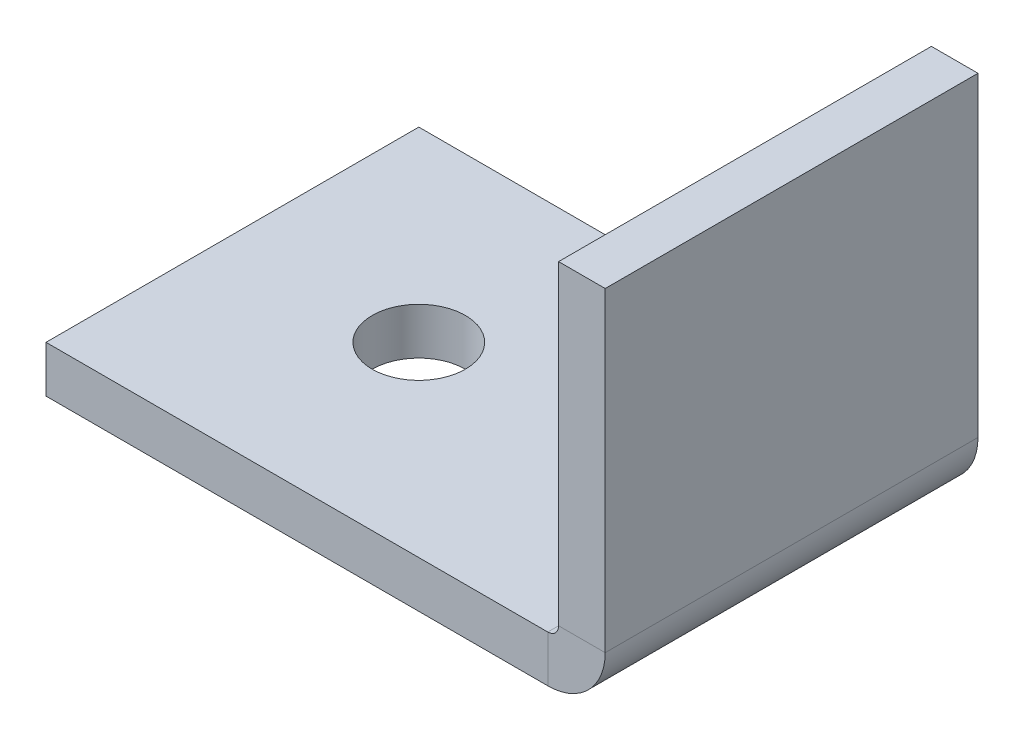
SolidWorks part; units mm, degrees
note: The reader was unsure of these and kept them because the rebuilt part matched: flange length of "Edge-Flange1".
ref_plane "Front Plane" through (0, 0, 0) normal (0, 0, 1) x (1, 0, 0)
ref_plane "Top Plane" through (0, 0, 0) normal (0, 1, 0) x (1, 0, 0)
ref_plane "Right Plane" through (0, 0, 0) normal (1, 0, 0) x (0, 0, -1)
sketch "Sketch1" plane through (0, 0, 0) normal (0, 1, 0) x (1, 0, 0)
  line L1 (-19.05, -12.7) -> (19.05, -12.7)
  line L2 (-19.05, -12.7) -> (-19.05, 12.7)
  line L3 (-19.05, 12.7) -> (19.05, 12.7)
  line L4 (19.05, -12.7) -> (19.05, 12.7)
  line L5 (-19.05, -12.7) -> (19.05, 12.7) construction
  line L6 (-19.05, 12.7) -> (19.05, -12.7) construction
  point P0 (0, 0)
  dimension "D1" = 25.4
  dimension "D2" = 38.1
base flange "Base-Flange1" sketch "Sketch1" thickness 3.175 reverse thickness direction no parameters "D1"=0.7366
edge flange "Edge-Flange1" sketch "Sketch9" flange angle 90 flange length 25.4 flange position material inside bend radius 0.7366 thickness 3.175 relief rectangular parameters "D6"=10
sketch "Sketch9" plane through (19.05, 0, 0) normal (1, 0, 0) x (0, 0, -1)
  line L2 (-12.7, 0) -> (-12.7, 22.225)
  line L3 (-12.7, 22.225) -> (12.7, 22.225)
  line L4 (12.7, 22.225) -> (12.7, 0)
  line L7 (-12.7, 0) -> (12.7, 0) construction
  line L8 (-12.7, 0) -> (12.7, 0)
bend "EdgeBend1" bend radius 0.7366 bend angle 90 parameters "D5"=1
sketch "Sketch10" plane through (0, 0, 0) normal (0, 1, 0) x (1, 0, 0)
  line L1 (19.05, 12.7) -> (19.05, -12.7) construction
  circle A1 centre (-6.35, 0) radius 3.175
  dimension "D1" = 6.35
  dimension "D2" = 25.4
extrude "Cut-Extrude1" cut sketch "Sketch10" against normal through all contours A1 normal cut yes
sketch "Bend-Lines1" [suppressed] plane through (0, 0, 0) normal (0, 1, 0) x (1, 0, 0)
sketch "Bounding-Box1" [suppressed] plane through (0, 0, 0) normal (0, 1, 0) x (1, 0, 0)
sheet metal parameters "Sheet-Metal1" thickness 3.175 parameters "D1"=0.7366
flat pattern "Flat-Pattern1" [suppressed]
sketch "Bend-Lines2" plane through (0, 0, 0) normal (0, 1, 0) x (1, 0, 0)
sketch3d "Bounding-Box2" [suppressed]
  line L0 (19.05, 12.7, 0) -> (-19.05, 12.7, 0) construction
  line L1 (19.05, -12.7, 0) -> (-19.05, -12.7, 0) construction
  line L2 (19.05, 12.7, 0) -> (19.05, -12.7, 0) construction
  line L3 (-19.05, 12.7, 0) -> (-19.05, -12.7, 0) construction
sheet metal parameters "Sheet-Metal2" thickness 3.175 parameters "D1"=0.7366
flat pattern "Flat-Pattern1"
sketch "Bend-Lines2" plane through (0, 0, 0) normal (0, 1, 0) x (1, 0, 0)
  line L0 (16.9637, -12.7) -> (16.9637, 12.7) construction
  line L1 (16.9637, -12.7) -> (16.9637, 12.7) construction
sketch3d "Bounding-Box2" [suppressed]
  line L0 (40.2775, 12.7, 0) -> (-19.05, 12.7, 0) construction
  line L1 (40.2775, -12.7, 0) -> (-19.05, -12.7, 0) construction
  line L2 (40.2775, 12.7, 0) -> (40.2775, -12.7, 0) construction
  line L3 (-19.05, 12.7, 0) -> (-19.05, -12.7, 0) construction
bend of the flat pattern "Flatten-<EdgeBend1>1"
sheet metal parameters "Sheet-Metal3" thickness 3.175 parameters "D1"=0.7366
flat pattern "Flat-Pattern1"
sketch "Bend-Lines2" plane through (0, 0, 0) normal (0, 1, 0) x (1, 0, 0)
  line L0 (16.9637, -12.7) -> (16.9637, 12.7) construction
  line L1 (16.9637, -12.7) -> (16.9637, 12.7) construction
sketch3d "Bounding-Box2" [suppressed]
  line L0 (40.2775, 12.7, 0) -> (-19.05, 12.7, 0) construction
  line L1 (40.2775, -12.7, 0) -> (-19.05, -12.7, 0) construction
  line L2 (40.2775, 12.7, 0) -> (40.2775, -12.7, 0) construction
  line L3 (-19.05, 12.7, 0) -> (-19.05, -12.7, 0) construction
bend of the flat pattern "Flatten-<EdgeBend1>1"
